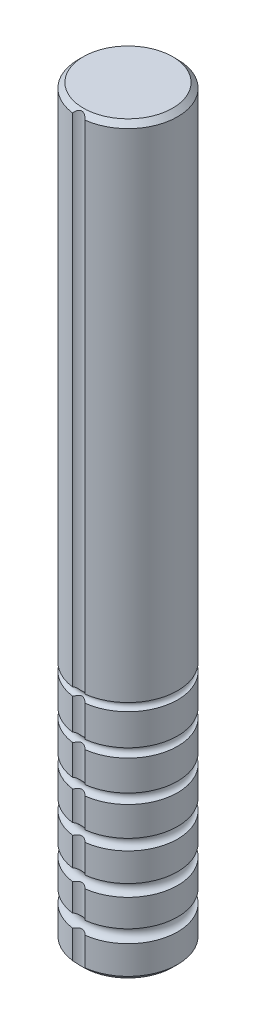
SolidWorks part; units mm, degrees
material "AISI 304"
ref_plane "前视基准面" through (0, 0, 0) normal (0, 0, 1) x (1, 0, 0)
ref_plane "上视基准面" through (0, 0, 0) normal (0, 1, 0) x (1, 0, 0)
ref_plane "右视基准面" through (0, 0, 0) normal (1, 0, 0) x (0, 0, -1)
sketch "草图1" plane through (0, 0, 0) normal (0, 1, 0) x (1, 0, 0)
  line L0 (-12.7236, 0) -> (21.95, 0) construction
  line L1 (0, 12.5715) -> (0, -13.0253) construction
  circle A0 centre (0, 0) radius 10
  circle A1 centre (0, 10.9) radius 1.58
  circle A2 centre (0, -10.9) radius 1.58
  point P9 (0, 9.32)
  dimension "D1" = 20
  dimension "D2" = 10.9
  dimension "D3" = 9.32
extrude "凸台-拉伸1" add sketch "草图1" along normal blind 150 contours A0 A2 A1 region at (0, 0, 0)
sketch "草图3" plane through (0, 0, 0) normal (0, 0, 1) x (1, 0, 0)
  line L0 (10, 0) -> (10, 150) construction
  line L1 (0, 0) -> (0, 26.297) construction
  line L2 (10, 0) -> (10, 150) construction
  circle A0 centre (10, 8) radius 1.3
  circle A8 centre (10, 32) radius 1
  circle A9 centre (10, 40) radius 0.9
  circle A10 centre (10, 48) radius 0.8
  circle A12 centre (10, 16) radius 1.2
  circle A13 centre (10, 24) radius 1.1
  dimension "D1" = 2.6
  dimension "D4" = 2.4
  dimension "D6" = 2.2
  dimension "D3" = 2
  dimension "D9" = 1.8
  dimension "D11" = 1.6
  dimension "D2" = 8
  dimension "D5" = 8
  dimension "D7" = 8
  dimension "D8" = 8
  dimension "D10" = 8
  dimension "D12" = 8
revolve "切除-旋转1" cut sketch "草图3" angle 360 about L1
chamfer "倒角1" distance 1 angle 45 2 edges at (-10, 0, 0) (-10, 150, 0)
